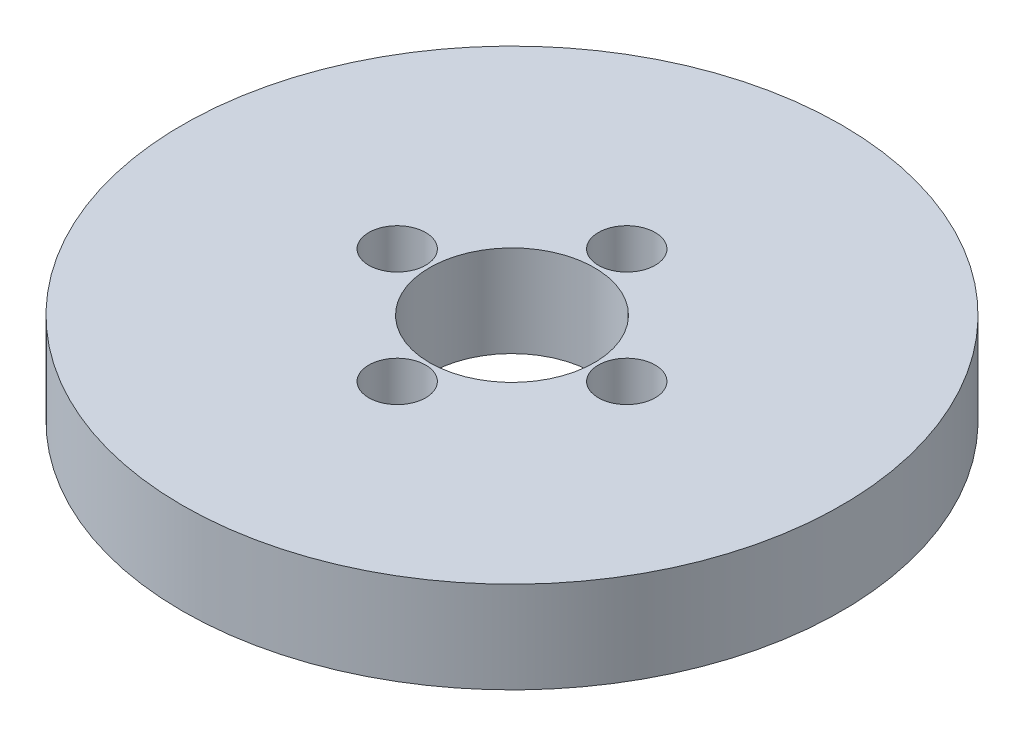
SolidWorks part; units mm, degrees
ref_plane "Front Plane" through (0, 0, 0) normal (0, 0, 1) x (1, 0, 0)
ref_plane "Top Plane" through (0, 0, 0) normal (0, 1, 0) x (1, 0, 0)
ref_plane "Right Plane" through (0, 0, 0) normal (1, 0, 0) x (0, 0, -1)
sketch "Sketch1" plane through (0, 0, 0) normal (0, 1, 0) x (1, 0, 0)
  circle A0 centre (0, 0) radius 90
  dimension "FLANGE_OD" = 180
extrude "Boss-Extrude1" add sketch "Sketch1" along normal blind 25
sketch "Sketch2" plane through (0, 0, 0) normal (0, 1, 0) x (1, 0, 0)
  circle A0 centre (0, 0) radius 22.5
  dimension "BORE_D" = 45
extrude "Cut-Extrude1" cut sketch "Sketch2" along normal through all
sketch "Sketch3" plane through (0, 25, 0) normal (0, 1, 0) x (1, 0, 0)
  circle A0 centre (0, 0) radius 31.3441 construction
  circle A1 centre (-31.3441, 0) radius 7.764
  dimension "BOLT_D" = 15.5279
  dimension "BOLT_PCD" = 62.6883
extrude "Cut-Extrude2" cut sketch "Sketch3" against normal blind 23.3908
pattern_circular "CirPattern1" count 4 over 360 about axis through (0, 0, 0) along (0, 1, 0) of "Cut-Extrude2"
